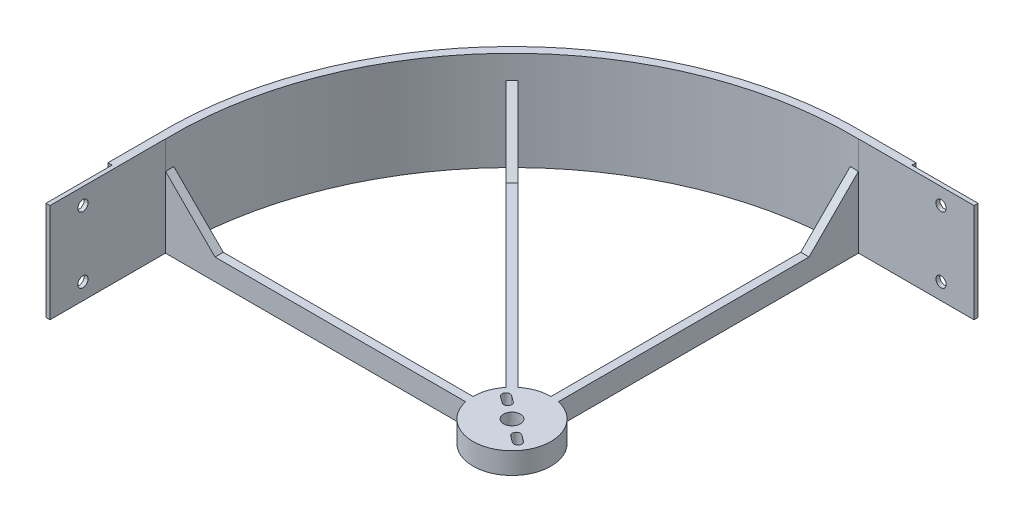
SolidWorks part; units mm, degrees
material "ABS"
ref_plane "Front Plane" through (0, 0, 0) normal (0, 0, 1) x (1, 0, 0)
ref_plane "Top Plane" through (0, 0, 0) normal (0, 1, 0) x (1, 0, 0)
ref_plane "Right Plane" through (0, 0, 0) normal (1, 0, 0) x (0, 0, -1)
sketch "Sketch1" plane through (0, 0, 0) normal (0, 1, 0) x (1, 0, 0)
  line L0 (0, 130.175) -> (0, 9.3426)
  line L1 (3.175, 9.3426) -> (3.175, 130.1363)
  line L2 (-92.0476, 92.0476) -> (0, 0) construction
  line L3 (-90.9182, 93.1633) -> (-5.7657, 8.0107)
  line L4 (-9.7388, -3.175) -> (-130.1363, -3.175)
  line L5 (-130.175, 0) -> (-9.3426, 0)
  line L6 (3.175, 9.3426) -> (3.175, 130.1363)
  line L7 (3.175, 130.1363) -> (3.175, 133.3122)
  line L8 (-130.1363, -3.175) -> (-133.3122, -3.175)
  line L9 (0, 0) -> (-130.175, 0) construction
  line L10 (-8.0089, 5.7638) -> (-93.1633, 90.9182)
  line L11 (0, 0) -> (0, 146.05) construction
  circle A0 centre (0, 0) radius 15
  arc A1 (3.175, 130.1363) -> (-130.1363, -3.175) centre (0, 0) ccw
  arc A2 (3.175, 133.3122) -> (-133.3122, -3.175) centre (0, 0) ccw
  point P21 (0, 0)
  dimension "D1" = 30
  dimension "D2" = 133.35
  dimension "D4" = 3.175
  dimension "D6" = 1.5875
  dimension "D3" = 3.175
  dimension "D7" = 1.5875
  dimension "D5" = 3.175
extrude "Boss-Extrude2" add sketch "Sketch1" along normal blind 8.255 contours A0
extrude "Boss-Extrude3" add sketch "Sketch1<6>" along normal blind 8.255 contours L5 A1 L4 A0 | L6 A1 L0 A0 | A1 L10 A0 region at (1.5882, 0, -72.5246) region at (-51.3161, 0, -51.3161) region at (-72.5246, 0, 1.5882)
sketch "Sketch1<6>" plane through (0, 0, 0) normal (0, 1, 0) x (1, 0, 0) same geometry as "Sketch1"
extrude "Boss-Extrude4" add sketch "Sketch1<7>" along normal blind 38.1 contours L7 A2 L8 A1 region at (-49.8095, 0, -122.3558)
sketch "Sketch1<7>" plane through (0, 0, 0) normal (0, 1, 0) x (1, 0, 0) same geometry as "Sketch1"
ref_plane "Plane1" through (-63.4806, 0, -63.4806) normal (0.7071, 0, 0.7071) x (0.7071, 0, -0.7071)
sketch "Sketch5" plane through (0, 8.255, 0) normal (0, 1, 0) x (1, 0, 0)
  line L0 (0, 0) -> (-92.0476, 92.0476) construction
  line L1 (0, 0) -> (15.8128, 15.8128) construction
  line L2 (-8.7797, 6.4967) -> (0, 0) construction
  line L3 (-6.3296, 4.6836) -> (-8.7797, 6.4967) construction
  line L4 (-7.2361, 3.4586) -> (-9.6862, 5.2716)
  line L5 (-5.4231, 5.9087) -> (-7.8732, 7.7217)
  line L6 (0, 0) -> (3.6216, 4.8943) construction
  line L7 (6.3296, -4.6836) -> (8.7797, -6.4967) construction
  line L8 (5.4231, -5.9087) -> (7.8732, -7.7217)
  line L9 (7.2361, -3.4586) -> (9.6862, -5.2716)
  line L10 (-90.9182, 93.1633) -> (-9.4245, 11.6696) construction
  arc A0 (5.4231, -5.9087) -> (7.2361, -3.4586) centre (6.3296, -4.6836) cw
  arc A1 (-7.2361, 3.4586) -> (-5.4231, 5.9087) centre (-6.3296, 4.6836) ccw
  arc A2 (-7.8732, 7.7217) -> (-9.6862, 5.2716) centre (-8.7797, 6.4967) ccw
  arc A3 (9.6862, -5.2716) -> (7.8732, -7.7217) centre (8.7797, -6.4967) cw
  circle A6 centre (0, 0) radius 3.25
  point P8 (-7.5546, 5.5901)
  point P17 (7.5546, -5.5901)
  point P18 (0, 0)
  dimension "D3" = 3.048
  dimension "D1" = 7.874
  dimension "D2" = 3.048
  dimension "D4" = 8.5
extrude "Cut-Extrude3" cut sketch "Sketch5" against normal blind 63.5
sketch "Sketch6" plane through (0, 0, 3.175) normal (0, 0, 1) x (1, 0, 0)
  line L0 (-14.6601, 0) -> (-133.3122, 0) construction
  line L1 (-130.1363, 38.1) -> (-131.7242, 38.1)
  line L2 (-130.1363, 38.1) -> (-130.1363, 0)
  line L3 (-130.1363, 0) -> (-131.7242, 0)
  line L4 (-131.7242, 38.1) -> (-131.7242, 0)
  line L5 (-130.1363, 38.1) -> (-133.3122, 38.1) construction
  point P7 (-131.7242, 38.1)
sketch "Sketch7" plane through (3.175, 0, 0) normal (1, 0, 0) x (0, 0, -1)
  line L0 (14.6601, 0) -> (133.3122, 0) construction
  line L1 (130.1363, 38.1) -> (131.7242, 38.1)
  line L2 (130.1363, 38.1) -> (130.1363, 0)
  line L3 (130.1363, 0) -> (131.7242, 0)
  line L4 (131.7242, 38.1) -> (131.7242, 0)
  line L5 (130.1363, 38.1) -> (133.3122, 38.1) construction
  line L6 (130.1363, 38.1) -> (130.1363, 8.255) construction
  point P7 (131.7242, 38.1)
ref_plane "Plane2" through (0, 0, 0) normal (0, 0, -1) x (-1, 0, 0)
sketch "Sketch10" plane through (0, 0, 0) normal (0, 0, -1) x (-1, 0, 0)
  line L0 (130.175, 27.305) -> (130.175, 8.255)
  line L4 (130.175, 8.255) -> (130.175, 38.1) construction
  line L5 (130.175, 8.255) -> (111.125, 8.255)
  line L6 (130.175, 8.255) -> (15, 8.255) construction
  line L7 (111.125, 8.255) -> (130.175, 27.305)
  dimension "D1" = 19.05
  dimension "D2" = 45
extrude "Boss-Extrude9" add sketch "Sketch10" against normal blind 3.175
ref_plane "Plane3" through (1.1225, 0, -1.1225) normal (0.7071, 0, -0.7071) x (-0.7071, 0, -0.7071)
ref_plane "Plane4" through (0, 0, 0) normal (-1, 0, 0) x (0, 0, 1)
sketch "Sketch13" plane through (0, 0, 0) normal (-1, 0, 0) x (0, 0, 1)
  line L0 (-130.175, 27.305) -> (-111.125, 8.255)
  line L1 (-130.175, 27.305) -> (-130.175, 8.255)
  line L2 (-130.175, 8.255) -> (-15, 8.255) construction
  line L3 (-130.175, 8.255) -> (-111.125, 8.255)
  line L4 (-130.175, 38.1) -> (-130.175, 8.255) construction
  dimension "D1" = 45
  dimension "D2" = 19.05
extrude "Boss-Extrude11" add sketch "Sketch13" against normal blind 3.175
sketch "Sketch14" plane through (1.1225, 0, -1.1225) normal (0.7071, 0, -0.7071) x (-0.7071, 0, -0.7071)
  line L0 (133.3403, 8.255) -> (111.1153, 8.255)
  line L1 (130.1653, 8.255) -> (14.9158, 8.255) construction
  line L2 (133.3403, 8.255) -> (133.3403, 32.3947)
  line L3 (133.3403, 32.3947) -> (111.1153, 8.255)
  dimension "D1" = 22.225
extrude "Boss-Extrude14" add sketch "Sketch14" against normal blind 3.175
ref_plane "Plane5" through (-131.7242, 0, 0) normal (-1, 0, 0) x (0, -1, 0)
sketch "Sketch15" plane through (-131.7242, 0, 0) normal (-1, 0, 0) x (0, -1, 0)
  line L1 (-38.1, 47.625) -> (0, 47.625)
  line L2 (-38.1, 47.625) -> (-38.1, 3.175)
  line L3 (-38.1, 3.175) -> (0, 3.175)
  line L4 (0, 47.625) -> (0, 3.175)
  dimension "D1" = 44.45
extrude "Boss-Extrude15" add sketch "Sketch15" against normal blind 1.524
ref_plane "Plane6" through (0, 0, -131.7242) normal (0, 0, -1) x (0, -1, 0)
sketch "Sketch16" plane through (0, 0, -131.7242) normal (0, 0, -1) x (0, -1, 0)
  line L1 (-38.1, -3.175) -> (0, -3.175)
  line L2 (-38.1, -3.175) -> (-38.1, -47.625)
  line L3 (-38.1, -47.625) -> (0, -47.625)
  line L4 (0, -3.175) -> (0, -47.625)
  dimension "D1" = 44.45
extrude "Boss-Extrude16" add sketch "Sketch16" against normal blind 1.524
sketch "Sketch17" plane through (0, 0, -131.7242) normal (0, 0, -1) x (-1, 0, 0)
  line L1 (-3.175, 38.1) -> (-47.625, 38.1) construction
  line L2 (19.05, 19.05) -> (-47.625, 19.05) construction
  line L3 (-47.625, 38.1) -> (-47.625, 0) construction
  circle A0 centre (-34.925, 31.75) radius 1.985
  circle A1 centre (-34.925, 6.35) radius 1.985
  dimension "D1" = 12.7
  dimension "D3" = 3.97
  dimension "D2" = 6.35
extrude "Cut-Extrude4" cut sketch "Sketch17" against normal blind 2.54
sketch "Sketch18" plane through (-131.7242, 0, 0) normal (-1, 0, 0) x (0, 0, 1)
  line L1 (25.4, 19.05) -> (47.625, 19.05) construction
  line L2 (47.625, 0) -> (47.625, 38.1) construction
  line L3 (47.625, 0) -> (47.625, 38.1) construction
  circle A0 centre (34.925, 31.75) radius 1.985
  circle A1 centre (34.925, 6.35) radius 1.985
  dimension "D1" = 3.97
  dimension "D2" = 12.7
  dimension "D3" = 12.7
extrude "Cut-Extrude5" cut sketch "Sketch18" against normal blind 2.54
sketch "Sketch19" plane through (-131.7242, 0, 0) normal (-1, 0, 0) x (0, 0, 1)
  line L0 (3.175, 0) -> (47.625, 0) construction
  line L1 (3.175, 38.1) -> (22.225, 38.1)
  line L2 (3.175, 38.1) -> (3.175, 0)
  line L3 (3.175, 0) -> (22.225, 0)
  line L4 (22.225, 38.1) -> (22.225, 0)
  dimension "D1" = 19.05
extrude "Boss-Extrude17" add sketch "Sketch19" along normal up to vertex (1.588 mm away) up to point (-133.3122, 38.1, 3.175)
sketch "Sketch20" plane through (0, 0, -131.7242) normal (0, 0, -1) x (-1, 0, 0)
  line L0 (-47.625, 0) -> (-3.175, 0) construction
  line L1 (-3.175, 38.1) -> (-22.225, 38.1)
  line L2 (-3.175, 38.1) -> (-3.175, 0)
  line L3 (-3.175, 0) -> (-22.225, 0)
  line L4 (-22.225, 38.1) -> (-22.225, 0)
  dimension "D1" = 19.05
extrude "Boss-Extrude18" add sketch "Sketch20" along normal up to vertex (1.588 mm away) up to point (3.175, 38.1, -133.3122)
